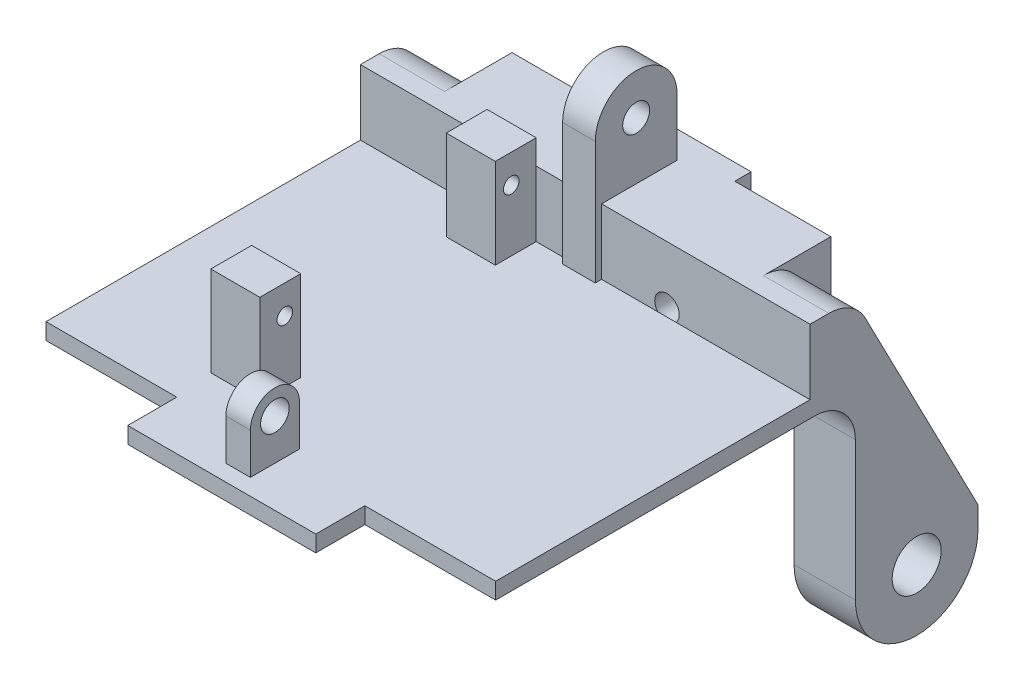
SolidWorks part; units mm, degrees
ref_plane "前视基准面" through (0, 0, 0) normal (0, 0, 1) x (1, 0, 0)
ref_plane "上视基准面" through (0, 0, 0) normal (0, 1, 0) x (1, 0, 0)
ref_plane "右视基准面" through (0, 0, 0) normal (1, 0, 0) x (0, 0, -1)
sketch "草图1" plane through (0, 0, 0) normal (0, 1, 0) x (1, 0, 0)
  line L1 (-27.5, -19.5) -> (27.5, -19.5)
  line L2 (-27.5, -19.5) -> (-27.5, 19.5)
  line L3 (-27.5, 19.5) -> (27.5, 19.5)
  line L4 (27.5, -19.5) -> (27.5, 19.5)
  line L5 (-27.5, -19.5) -> (27.5, 19.5) construction
  line L6 (-27.5, 19.5) -> (27.5, -19.5) construction
  point P0 (0, 0)
  dimension "D1" = 55
  dimension "D2" = 39
extrude "凸台-拉伸1" add sketch "草图1" along normal blind 2
sketch "草图2" plane through (0, 2, 0) normal (0, 1, 0) x (1, 0, 0)
  line L0 (-27.5, -19.5) -> (27.5, -19.5) construction
  line L1 (-11.5, -19.5) -> (11.5, -19.5)
  line L2 (-11.5, -19.5) -> (-11.5, -25.5)
  line L3 (-11.5, -25.5) -> (11.5, -25.5)
  line L4 (11.5, -19.5) -> (11.5, -25.5)
  line L5 (27.5, 19.5) -> (-27.5, 19.5) construction
  point P9 (0, -25.5)
  dimension "D1" = 23
  dimension "D2" = 45
extrude "凸台-拉伸2" add sketch "草图2" against normal blind 2
sketch "草图3" plane through (0, 2, 0) normal (0, 1, 0) x (1, 0, 0)
  line L1 (-6, -14.8415) -> (-12, -14.8415)
  line L2 (-6, -14.8415) -> (-6, -9.8415)
  line L3 (-6, -9.8415) -> (-12, -9.8415)
  line L4 (-12, -14.8415) -> (-12, -9.8415)
  line L6 (-6, 13.9585) -> (-12, 13.9585)
  line L7 (-6, 13.9585) -> (-6, 18.9585)
  line L8 (-6, 18.9585) -> (-12, 18.9585)
  line L9 (-12, 13.9585) -> (-12, 18.9585)
  dimension "D1" = 6
  dimension "D2" = 23.8
  dimension "D3" = 6
  dimension "D4" = 6
  dimension "D5" = 6
  dimension "D6" = 5
  dimension "D7" = 5
extrude "凸台-拉伸3" add sketch "草图3" along normal blind 11
sketch "草图5" plane through (-12, 0, 0) normal (-1, 0, 0) x (0, 0, 1)
  line L0 (-13.9585, 13) -> (-13.9585, 2) construction
  line L1 (9.8415, 13) -> (9.8415, 2) construction
  line L2 (-19.5, 2) -> (19.5, 2) construction
  line L3 (9.8415, 2) -> (14.8415, 2) construction
  circle A0 centre (-15.9085, 9.5) radius 0.95
  circle A1 centre (11.7915, 9.5) radius 0.95
  dimension "D1" = 1.95
  dimension "D2" = 1.95
  dimension "D3" = 7.5
  dimension "D4" = 7.5
  dimension "D5" = 27.7
  dimension "D6" = 1.9
  dimension "D7" = 1.9
extrude "切除-拉伸1" cut sketch "草图5" against normal blind 11
sketch "草图6" plane through (0, 2, 0) normal (0, 1, 0) x (1, 0, 0)
  line L0 (27.5, -19.5) -> (27.5, 19.5) construction
  line L1 (-27.5, 19.5) -> (27.5, 19.5)
  line L2 (-27.5, 19.5) -> (-27.5, 18.9585)
  line L3 (-27.5, 18.9585) -> (27.5, 18.9585)
  line L4 (27.5, 19.5) -> (27.5, 18.9585)
  line L5 (-6, 18.9585) -> (-12, 18.9585) construction
extrude "凸台-拉伸4" add sketch "草图6" along normal blind 8
sketch "草图8" plane through (0, 0, 0) normal (1, 0, 0) x (0, 0, -1)
  line L0 (28.1899, 17) -> (28.1899, 0)
  line L1 (-19.5, 2) -> (18.9585, 2) construction
  line L2 (18.1899, 17) -> (18.1899, 0)
  line L4 (18.1899, 0) -> (28.1899, 0)
  line L7 (-19.5, 0) -> (19.5, 0) construction
  arc A0 (28.1899, 17) -> (18.1899, 17) centre (23.1899, 17) ccw
  circle A1 centre (23.1899, 17) radius 1.65
  dimension "D1" = 15
  dimension "D2" = 10
  dimension "D3" = 3.3
extrude "凸台-拉伸6" add sketch "草图8" along normal mid plane 4
sketch "草图10" plane through (0, 2, 0) normal (0, 1, 0) x (1, 0, 0)
  line L0 (-11.5, -25.5) -> (11.5, -25.5) construction
  line L1 (-1.5, -17.5) -> (1.5, -17.5)
  line L2 (-1.5, -17.5) -> (-1.5, -23.5)
  line L3 (-1.5, -23.5) -> (1.5, -23.5)
  line L4 (1.5, -17.5) -> (1.5, -23.5)
  point P7 (0, -17.5)
  dimension "D1" = 2
  dimension "D2" = 3
  dimension "D3" = 6
extrude "凸台-拉伸7" add sketch "草图10" along normal blind 8
sketch "草图11" plane through (0, 0, -18.9585) normal (0, 0, 1) x (1, 0, 0)
  line L0 (-2, 10) -> (-27.5, 10) construction
  circle A0 centre (-10, 3) radius 1.5
  dimension "D1" = 10
  dimension "D2" = 3
  dimension "D3" = 7
extrude "切除-拉伸3" cut sketch "草图11" against normal blind 13
sketch "草图12" plane through (-27.5, 0, 0) normal (-1, 0, 0) x (0, 0, 1)
  line L1 (-19.5, 0) -> (4.0888, 0)
  line L2 (-19.5, 0) -> (19.5, 0) construction
  line L3 (-19.5, 10) -> (-19.5, 0) construction
  line L4 (-39.5, -22) -> (-39.5, 10)
  line L5 (-19.5, 10) -> (-39.5, 10)
  line L6 (-24.5, -22) -> (-24.5, 0)
  line L7 (-24.5, 0) -> (-19.5, 0)
  line L8 (-19.5, 10) -> (-19.5, 0)
  arc A0 (-39.5, -22) -> (-24.5, -22) centre (-32, -22) ccw
  circle A2 centre (-32, -22) radius 3
  line M7 (-19.5, 10) -> (-19.5, 0)
  dimension "D1" = 15
  dimension "D5" = 6
  dimension "D2" = 22
  dimension "D3" = 12.5
extrude "凸台-拉伸8" add sketch "草图12" against normal blind 7.5 contours L4 A0 L6 L7 L5 A2 M7 region at (-27.5, -7.1737, -31.1527)
sketch "草图13" plane through (0, 0, 0) normal (0, -1, 0) x (1, 0, 0)
  line L0 (-11.5, 25.5) -> (11.5, 25.5) construction
  line L1 (-5, 21) -> (5, 21)
  line L2 (-5, 21) -> (-5, 17.3)
  line L3 (-5, 17.3) -> (5, 17.3)
  line L4 (5, 21) -> (5, 17.3)
  line L5 (-5, 21) -> (5, 17.3) construction
  line L6 (-5, 17.3) -> (5, 21) construction
  point P0 (0, 19.15)
  dimension "D1" = 10
  dimension "D2" = 4.5
  dimension "D3" = 3.7
extrude "凸台-拉伸9" add sketch "草图13" along normal blind 1
mirror "镜向1" about plane through (0, 0, 0) normal (1, 0, 0) of "凸台-拉伸8", "切除-拉伸3"
fillet "圆角3" 2 edges at (0, 10, 17.5) (0, 10, 23.5) type full round first side face at (0, 6, 17.5) second side face at (0, 6, 23.5) middle face at (0, 10, 20.5)
sketch "草图15" plane through (-1.5, 0, 0) normal (-1, 0, 0) x (0, 0, 1)
  circle A0 centre (20.5, 7) radius 1.75
  dimension "D1" = 3.5
extrude "切除-拉伸5" cut sketch "草图15" against normal blind 23
sketch "草图16" plane through (0, 0, -19.5) normal (0, 0, -1) x (-1, 0, 0)
  line L0 (-20, 10) -> (-2, 10) construction
  line L1 (-7.75, 10) -> (7.75, 10)
  line L2 (-7.75, 10) -> (-7.75, 6)
  line L3 (-7.75, 6) -> (7.75, 6)
  line L4 (7.75, 10) -> (7.75, 6)
  point P6 (0, 6)
  dimension "D1" = 15.5
  dimension "D2" = 4
extrude "凸台-拉伸10" add sketch "草图16" along normal blind 20
sketch "草图17" plane through (0, 0, -19.5) normal (0, 0, -1) x (-1, 0, 0)
  line L6 (-20, 0) -> (-2, 0)
  line L7 (-20, 0) -> (-2, 0)
  line L8 (-20, 10) -> (-20, 0)
  line L10 (-7.75, 6) -> (-7.75, 10)
  line L11 (-7.75, 10) -> (-20, 10)
  line L12 (-2, 0) -> (-2, 6)
  line L14 (-2, 0) -> (-2, 6)
  line L15 (-7.75, 6) -> (-7.75, 10)
  line L16 (-2, 6) -> (-7.75, 6)
  line L18 (-2, 6) -> (-7.75, 6)
  line L21 (-7.75, 10) -> (-20, 10)
  line L32 (-20, 10) -> (-20, 0)
  line L33 (7.75, 6) -> (2, 6)
  line L34 (2, 6) -> (2, 0)
  line L35 (2, 0) -> (20, 0)
  line L36 (20, 0) -> (20, 10)
  line L37 (20, 10) -> (7.75, 10)
  line L38 (7.75, 10) -> (7.75, 6)
  line L39 (7.75, 6) -> (2, 6)
  line L40 (2, 6) -> (2, 0)
  line L41 (2, 0) -> (20, 0)
  line L42 (20, 0) -> (20, 10)
  line L43 (20, 10) -> (7.75, 10)
  line L44 (7.75, 10) -> (7.75, 6)
  circle A0 centre (10, 3) radius 1.5 construction
  circle A1 centre (-10, 3) radius 1.5 construction
  circle A2 centre (10, 3) radius 1.5
  circle A3 centre (-10, 3) radius 1.5
  dimension "D1" = 0
  dimension "D2" = 0
extrude "凸台-拉伸11" add sketch "草图17" along normal blind 10
fillet "圆角4" radius 10 2 edges at (23.75, 10, -39.5) (-23.75, 10, -39.5)
sketch "草图18" plane through (0, 10, 0) normal (0, 1, 0) x (1, 0, 0)
  line L0 (-7.75, 39.5) -> (7.75, 39.5) construction
  line L1 (-14.1233, 41.9545) -> (12.4415, 41.9545)
  line L2 (-14.1233, 41.9545) -> (-14.1233, 31.5)
  line L3 (-14.1233, 31.5) -> (12.4415, 31.5)
  line L4 (12.4415, 41.9545) -> (12.4415, 31.5)
  dimension "D1" = 8
extrude "切除-拉伸6" cut sketch "草图18" against normal blind 10
sketch "草图19" plane through (27.5, 0, 0) normal (1, 0, 0) x (0, 0, -1)
  line L0 (24.3, 10) -> (39.5, -19.3956)
  line L1 (39.5, -22) -> (39.5, 0) construction
  line L2 (24.3, 10) -> (39.5, 10)
  line L3 (39.5, 10) -> (39.5, -19.3956)
  dimension "D1" = 15.2
extrude "切除-拉伸7" cut sketch "草图19" against normal blind 8
sketch "草图20" plane through (-27.5, 0, 0) normal (-1, 0, 0) x (0, 0, 1)
  line L0 (-24.3, 10) -> (-39.5, 10)
  line L1 (-39.5, 10) -> (-39.5, -19.3956)
  line L8 (-39.5, -19.3956) -> (-39.5, -22)
  line L9 (-24.3, 10) -> (-39.5, -19.3956)
  line L10 (-18.9585, 10) -> (-24.3, 10)
  line L11 (-18.9585, 2) -> (-18.9585, 10)
  line L12 (19.5, 2) -> (-18.9585, 2)
  line L13 (19.5, 0) -> (19.5, 2)
  line L14 (-24.5, 0) -> (19.5, 0)
  line L15 (-24.5, -22) -> (-24.5, 0)
  line L17 (-24.3, 10) -> (-39.5, -19.3956)
  arc A1 (-39.5, -22) -> (-24.5, -22) centre (-32, -22) ccw
  dimension "D1" = 0
extrude "切除-拉伸8" cut sketch "草图20" against normal blind 8
fillet "圆角6" radius 5 4 edges at (23.75, 0, -24.5) (-23.75, 0, -24.5) (23.5, 10, -24.3) (-23.5, 10, -24.3)
sketch "草图21" plane through (0, -1, 0) normal (0, -1, 0) x (1, 0, 0)
  line L0 (-11.5, 25.5) -> (11.5, 25.5) construction
  line L1 (-27.5, -19.5) -> (-27.5, 19.5) construction
  circle A0 centre (0, 19.15) radius 1.4
  dimension "D1" = 2.8
  dimension "D2" = 6.35
  dimension "D3" = 27.5
extrude "切除-拉伸9" cut sketch "草图21" against normal blind 4
